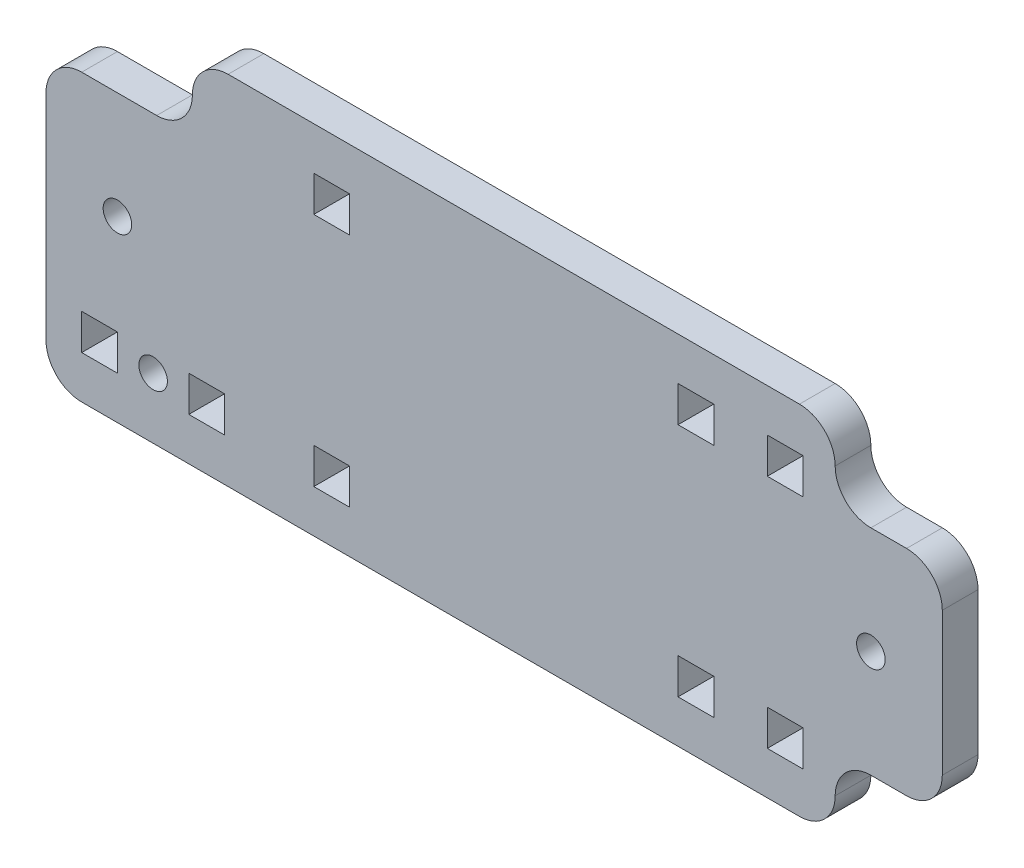
SolidWorks part; units mm, degrees
ref_plane "Plan de face" through (0, 0, 0) normal (0, 0, 1) x (1, 0, 0)
ref_plane "Plan de dessus" through (0, 0, 0) normal (0, 1, 0) x (1, 0, 0)
ref_plane "Plan de droite" through (0, 0, 0) normal (1, 0, 0) x (0, 0, -1)
sketch "Esquisse1" plane through (0, 0, 0) normal (0, 0, 1) x (1, 0, 0)
  line L0 (15, 30) -> (15, 40)
  line L2 (0, 0) -> (0, 30) construction
  line L3 (0, 30) -> (15, 30)
  line L4 (120, 0) -> (120, 30)
  line L5 (15, 40) -> (105, 40)
  line L6 (105, 40) -> (105, 30)
  line L7 (105, 30) -> (120, 30)
  line L8 (0, 15) -> (120, 15) construction
  line L9 (24.5, 29) -> (95.5, 29) construction
  line L10 (24.5, 29) -> (24.5, 1) construction
  line L11 (24.5, 1) -> (95.5, 1) construction
  line L12 (95.5, 29) -> (95.5, 1) construction
  line L13 (105, 0) -> (120, 0)
  line L14 (105, -10) -> (105, 0)
  line L15 (15, -10) -> (105, -10)
  line L18 (60, 40) -> (60, 15) construction
  line L19 (88, 34) -> (83, 34)
  line L20 (32, 34) -> (37, 34)
  line L21 (32, 34) -> (32, 29)
  line L22 (32, 29) -> (37, 29)
  line L23 (37, 34) -> (37, 29)
  line L24 (88, 34) -> (88, 29)
  line L25 (83, 34) -> (83, 29)
  line L26 (88, 29) -> (83, 29)
  line L27 (88, 1) -> (83, 1)
  line L28 (88, -4) -> (88, 1)
  line L29 (88, -4) -> (83, -4)
  line L30 (83, -4) -> (83, 1)
  line L31 (32, -4) -> (32, 1)
  line L32 (32, 1) -> (37, 1)
  line L33 (37, -4) -> (37, 1)
  line L34 (32, -4) -> (37, -4)
  line L35 (-5.5, 30) -> (0, 30)
  line L44 (95.5, 1) -> (100.5, 1)
  line L45 (95.5, 1) -> (95.5, -4)
  line L46 (95.5, -4) -> (100.5, -4)
  line L47 (100.5, 1) -> (100.5, -4)
  line L48 (95.5, 29) -> (100.5, 29)
  line L49 (95.5, 29) -> (95.5, 34)
  line L50 (95.5, 34) -> (100.5, 34)
  line L51 (100.5, 29) -> (100.5, 34)
  line L52 (-5.5, 30) -> (-5.5, -10)
  line L53 (-5.5, -10) -> (15, -10)
  line L54 (-5.5, 15) -> (0, 15) construction
  line L55 (-0.5, 1) -> (4.5, 1)
  line L56 (-0.5, 1) -> (-0.5, -4)
  line L57 (-0.5, -4) -> (4.5, -4)
  line L58 (4.5, 1) -> (4.5, -4)
  line L59 (14.5, 1) -> (19.5, 1)
  line L60 (14.5, 1) -> (14.5, -4)
  line L61 (14.5, -4) -> (19.5, -4)
  line L62 (19.5, 1) -> (19.5, -4)
  line L63 (4.5, -1.5) -> (14.5, -1.5) construction
  circle A0 centre (10, 15) radius 2 construction
  circle A2 centre (110, 15) radius 2
  circle A3 centre (4.5, 15) radius 2
  circle A4 centre (9.5, -1.5) radius 2
  point P18 (10, 20)
  point P19 (24.5, 15)
  point P22 (60, 29)
  point P43 (34.5, 34)
  point P60 (-0.5, -1.5)
  point P68 (0, 0)
  point P69 (9.5, -1.5)
  point P70 (10, 20)
  point P71 (110, 0)
  point P72 (110, 20)
  point P73 (10, 20)
  point P74 (0, 0)
  point P75 (0, 0)
  point P76 (110, 20)
  point P77 (102.5, 0)
  point P78 (13.4936, 20)
  point P79 (0, 0)
  dimension "D8" = 4
  dimension "D19" = 4
  dimension "D1" = 120
  dimension "D2" = 30
  dimension "D3" = 50
  dimension "D4" = 90
  dimension "D6" = 71
  dimension "D7" = 28
  dimension "D9" = 10
  dimension "D10" = 5
  dimension "D11" = 7.5
  dimension "D12" = 9.5
  dimension "D13" = 6
  dimension "D14" = 10
  dimension "D15" = 5
  dimension "D16" = 5
  dimension "D17" = 37.5
  dimension "D18" = 10
extrude "Boss.-Extru.1" add sketch "Esquisse1" along normal blind 5
fillet "Congé1" radius 5 10 edges at (105, -10, 2.5) (105, 0, 2.5) (120, 0, 2.5) (120, 30, 2.5) (105, 30, 2.5) (105, 40, 2.5) (15, 40, 2.5) (15, 30, 2.5) (-5.5, -10, 2.5) (-5.5, 30, 2.5)
